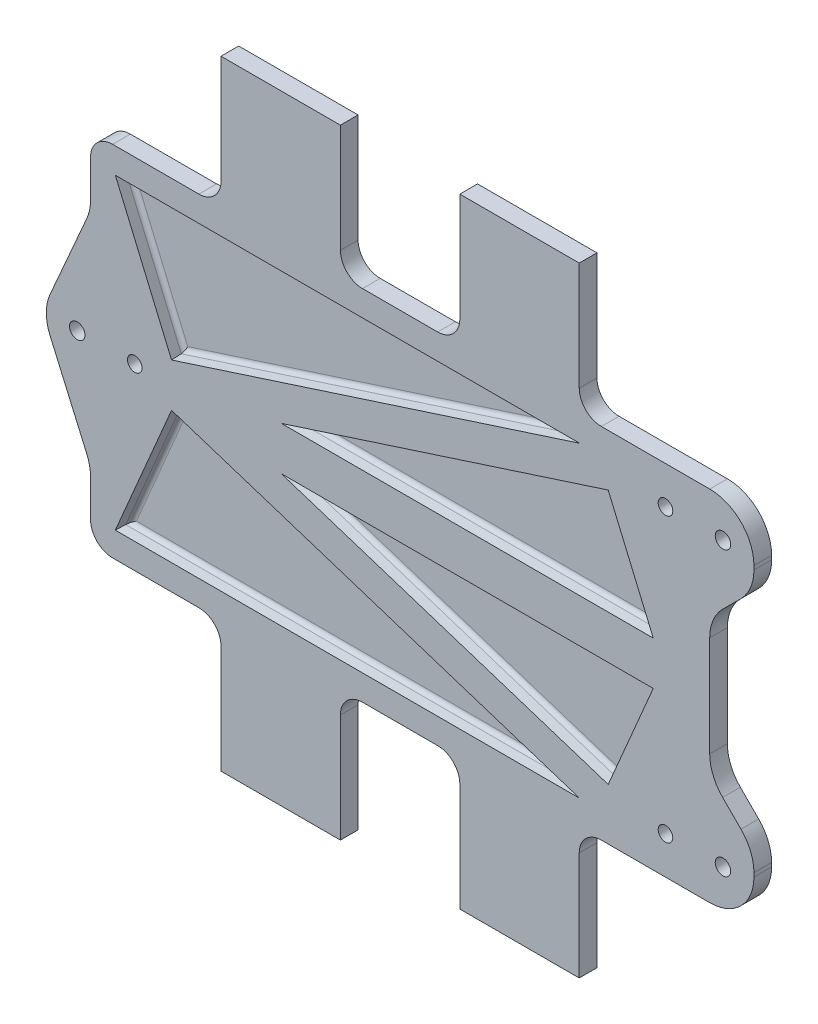
SolidWorks part; units mm, degrees
material "Ceramic Porcelain"
ref_plane "Front Plane" through (0, 0, 0) normal (0, 0, 1) x (1, 0, 0)
ref_plane "Top Plane" through (0, 0, 0) normal (0, 1, 0) x (1, 0, 0)
ref_plane "Right Plane" through (0, 0, 0) normal (1, 0, 0) x (0, 0, -1)
sketch "Sketch1" plane through (0, 0, 0) normal (0, 0, 1) x (1, 0, 0)
  line L0 (140, 70) -> (-19.1725, 70) construction
  line L1 (0, 0) -> (140, 0)
  line L2 (0, 0) -> (0, 42.9273)
  line L3 (0, 140) -> (140, 140)
  line L4 (140, 0) -> (140, 140)
  line L5 (-9.164, 74.0025) -> (-0.836, 93.0702)
  line L6 (-9.164, 65.9975) -> (-0.836, 46.9298)
  line L7 (0, 97.0727) -> (0, 140)
  line L8 (0, 97.0727) -> (0, 42.9273) construction
  arc A0 (-9.164, 65.9975) -> (-9.164, 74.0025) centre (0, 70) cw
  arc A1 (-0.836, 93.0702) -> (0, 97.0727) centre (-10, 97.0727) ccw
  arc A2 (-0.836, 46.9298) -> (0, 42.9273) centre (-10, 42.9273) cw
  point P14 (0, 94.9841)
  dimension "D2" = 10
  dimension "D3" = 10
  dimension "D4" = 10
  dimension "D1" = 140
extrude "Boss-Extrude1" add sketch "Sketch1" along normal blind 4
sketch "Sketch2" plane through (0, 0, 4) normal (0, 0, 1) x (1, 0, 0)
  line L0 (0, 42.9273) -> (0, 0) construction
  line L1 (5, 5) -> (27, 5)
  line L2 (5, 5) -> (5, 27)
  line L3 (5, 27) -> (27, 27)
  line L4 (27, 5) -> (27, 27)
  line L5 (0, 0) -> (140, 0) construction
  dimension "D1" = 22
  dimension "D2" = 5
  dimension "D3" = 5
extrude "Cut-Extrude2" [suppressed] cut sketch "Sketch2" against normal blind 3
chamfer "Chamfer1" [suppressed] distance 3 angle 15
fillet "Fillet3" [suppressed] radius 1
fillet "Fillet4" [suppressed] radius 1
pattern_linear "LPattern1" [suppressed] count 5 spacing 27 count 5 spacing 27 of bodies 103
sketch "Sketch3" plane through (0, 0, 4) normal (0, 0, 1) x (1, 0, 0)
  line L0 (0, 0) -> (140, 0) construction
  line L1 (0, 0) -> (29.5, 0)
  line L2 (0, 0) -> (0, 29.5)
  line L3 (0, 29.5) -> (29.5, 29.5)
  line L4 (29.5, 0) -> (29.5, 29.5)
  line L5 (56.5, 0) -> (83.5, 0)
  line L6 (56.5, 0) -> (56.5, 29.5)
  line L7 (56.5, 29.5) -> (83.5, 29.5)
  line L8 (83.5, 0) -> (83.5, 29.5)
  line L9 (70, 0) -> (70, 140) construction
  line L10 (140, 140) -> (110.5, 140)
  line L11 (140, 140) -> (140, 110.5)
  line L15 (110.5, 0) -> (110.5, 29.5)
  line L16 (140, 29.5) -> (110.5, 29.5)
  line L17 (140, 0) -> (140, 29.5)
  line L18 (140, 0) -> (110.5, 0)
  line L19 (140, 110.5) -> (110.5, 110.5)
  line L20 (110.5, 140) -> (110.5, 110.5)
  line L21 (29.5, 140) -> (29.5, 110.5)
  line L22 (0, 110.5) -> (29.5, 110.5)
  line L23 (0, 140) -> (0, 110.5)
  line L24 (0, 140) -> (29.5, 140)
  line L25 (0, 0) -> (140, 140) construction
  line L31 (83.5, 140) -> (83.5, 110.5)
  line L32 (56.5, 110.5) -> (83.5, 110.5)
  line L33 (56.5, 140) -> (56.5, 110.5)
  line L34 (56.5, 140) -> (83.5, 140)
  dimension "D1" = 29.5
  dimension "D2" = 56.5
  dimension "D3" = 27
extrude "Cut-Extrude3" cut sketch "Sketch3" against normal through all
sketch "Sketch9" plane through (0, 0, 0) normal (0, 0, -1) x (-1, 0, 0)
  line L0 (-140, 110.5) -> (-150, 110.5)
  line L1 (-150, 110.5) -> (-150, 95.5)
  line L2 (-150, 95.5) -> (-140, 85.5)
  line L3 (-140, 29.5) -> (-140, 110.5) construction
  line L4 (-140, 70) -> (-101.7414, 70) construction
  line L5 (-140, 110.5) -> (-140, 85.5)
  line L6 (-140, 29.5) -> (-140, 54.5)
  line L7 (-150, 44.5) -> (-140, 54.5)
  line L8 (-150, 29.5) -> (-150, 44.5)
  line L9 (-140, 29.5) -> (-150, 29.5)
  dimension "D1" = 10
  dimension "D2" = 15
  dimension "D3" = 25
extrude "Boss-Extrude2" add sketch "Sketch9" against normal up to surface (4 mm away) up to face at (53.0607, 70, 4)
fillet "Fillet5" radius 10 6 edges at (150, 29.5, 2) (150, 44.5, 2) (140, 54.5, 2) (150, 95.5, 2) (150, 110.5, 2)
sketch "Sketch10" [suppressed] plane through (0, 0, 6) normal (0, 0, 1) x (1, 0, 0)
  line L0 (127.2327, 102) -> (127.2327, 108.7673)
  line L1 (112.2327, 108.7673) -> (135.7673, 108.7673) construction
  line L2 (127.2327, 108.7673) -> (135.7673, 108.7673)
  line L3 (134, 95.2327) -> (135.7673, 95.2327)
  line L4 (135.7673, 108.7673) -> (135.7673, 85.2327) construction
  line L5 (135.7673, 95.2327) -> (135.7673, 108.7673)
  line L6 (127.2327, 38) -> (127.2327, 31.2327)
  line L7 (135.7673, 31.2327) -> (112.2327, 31.2327) construction
  line L8 (127.2327, 31.2327) -> (135.7673, 31.2327)
  line L9 (135.7673, 31.2327) -> (135.7673, 44.7673)
  line L10 (135.7673, 54.7673) -> (135.7673, 31.2327) construction
  line L11 (135.7673, 44.7673) -> (134, 44.7673)
  line L12 (4.2327, 74.1422) -> (6, 74.1422)
  line L13 (4.2327, 58.2327) -> (4.2327, 81.7673) construction
  line L14 (4.2327, 74.1422) -> (4.2327, 65.8578)
  line L15 (4.2327, 65.8578) -> (6, 65.8578)
  arc A1 (134, 44.7673) -> (127.2327, 38) centre (134, 38) ccw
  arc A2 (6, 65.8578) -> (6, 74.1422) centre (6, 70) ccw
  arc A3 (127.2327, 102) -> (134, 95.2327) centre (134, 102) ccw
extrude "Boss-Extrude3" [suppressed] add sketch "Sketch10" against normal up to surface (3 mm away)
hole_wizard "CSK for M3 Flat Head Machine Screw1" positions "Sketch6" profile "Sketch5" countersink size "M3" standard "Ansi Metric" end condition through all
sketch "Sketch6" plane through (0, 0, 0) normal (0, 0, -1) x (-1, 0, 0)
  line L0 (3.5733, 70) -> (-140, 70) construction
  line L4 (-140, 58.6421) -> (-140, 81.3579) construction
  line L5 (-130, 102) -> (-130, 38) construction
  point P0 (-10, 70)
  point P20 (-130, 102)
  point P22 (-130, 38)
  dimension "D1" = 10
  dimension "D2" = 10
  dimension "D3" = 32
  dimension "D4" = 64
sketch "Sketch5" plane through (10, 70, 0) normal (1, 0, 0) x (0, 1, 0)
  line L0 (0, 0) -> (0, 4)
  line L1 (0, 4) -> (1.65, 4)
  line L2 (1.65, 4) -> (1.65, 1.35)
  line L3 (1.65, 1.35) -> (3, 0)
  line L5 (3, 0) -> (0, 0)
  line L6 (-1.65, 1.35) -> (-3, 0) construction
  line L11 (0, -6.35) -> (0, 107.95) construction
  dimension "Thru Hole Dia." = 3.3
  dimension "Thru Hole Depth" = 4
  dimension "Near C'Sink Dia." = 6
  dimension "Near C'Sink Angle" = 90
sketch "Sketch8" plane through (0, 0, 0) normal (0, 0, -1) x (-1, 0, 0)
  line L0 (-140, 70) -> (10, 70) construction
  line L1 (-140, 58.6421) -> (-140, 81.3579) construction
  line L2 (-130, 102) -> (-143, 102) construction
  line L3 (-130, 38) -> (-143, 38) construction
  arc A0 (9.164, 65.9975) -> (9.164, 74.0025) centre (0, 70) ccw construction
  circle A1 centre (3, 70) radius 1.75
  circle A2 centre (-10, 70) radius 1.65 construction
  circle A3 centre (-143, 102) radius 1.75
  circle A4 centre (-143, 38) radius 1.75
  dimension "D1" = 13
  dimension "D2" = 3.5
  dimension "D3" = 13
extrude "Cut-Extrude4" cut sketch "Sketch8" against normal through all
fillet "Fillet6" radius 5 10 edges at (29.5, 29.5, 2) (83.5, 29.5, 2) (56.5, 29.5, 2) (110.5, 29.5, 2) (29.5, 110.5, 2) (83.5, 110.5, 2) (56.5, 110.5, 2) (110.5, 110.5, 2) (0, 110.5, 2) (0, 29.5, 2)
sketch "Sketch11" plane through (0, 0, 4) normal (0, 0, 1) x (1, 0, 0)
  line L0 (140, 70) -> (-10, 70) construction
  line L1 (140, 58.6421) -> (140, 81.3579) construction
  line L2 (110.5872, 104.7584) -> (5.6009, 104.7584)
  line L3 (5.6009, 104.7584) -> (18.3195, 74.9275)
  line L4 (18.3195, 74.9275) -> (110.5872, 104.7584)
  line L5 (117.0488, 98.8234) -> (43.1382, 74.9275)
  line L6 (43.1382, 74.9275) -> (127.237, 74.9275)
  line L7 (127.237, 74.9275) -> (117.0488, 98.8234)
  line L8 (127.237, 65.0725) -> (117.0488, 41.1766)
  line L9 (43.1382, 65.0725) -> (127.237, 65.0725)
  line L10 (117.0488, 41.1766) -> (43.1382, 65.0725)
  line L11 (18.3195, 65.0725) -> (110.5872, 35.2416)
  line L12 (5.6009, 35.2416) -> (18.3195, 65.0725)
  line L13 (110.5872, 35.2416) -> (5.6009, 35.2416)
  arc A0 (-9.164, 74.0025) -> (-9.164, 65.9975) centre (0, 70) ccw construction
extrude "Cut-Extrude5" cut sketch "Sketch11" against normal offset from surface (3 mm away) 1 up to face at (141.25, 38, 0)
chamfer "Chamfer2" distance 3 angle 5 12 edges at (64.4533, 50.157, 1) (58.094, 35.2416, 1) (11.9602, 50.157, 1) (122.1429, 53.1245, 1) (80.0935, 53.1245, 1) (85.1876, 65.0725, 1) (85.1876, 74.9275, 1) (80.0935, 86.8755, 1) (122.1429, 86.8755, 1) (11.9602, 89.843, 1) (58.094, 104.7584, 1) (64.4533, 89.843, 1) first distance on face at (64.4533, 50.157, 2.5) first distance on face at (58.094, 35.2416, 2.5) first distance on face at (11.9602, 50.157, 2.5) first distance on face at (122.1429, 53.1245, 2.5) first distance on face at (80.0935, 53.1245, 2.5) first distance on face at (85.1876, 65.0725, 2.5) first distance on face at (85.1876, 74.9275, 2.5) first distance on face at (80.0935, 86.8755, 2.5) first distance on face at (122.1429, 86.8755, 2.5) first distance on face at (11.9602, 89.843, 2.5) first distance on face at (58.094, 104.7584, 2.5) first distance on face at (64.4533, 89.843, 2.5)
fillet "Fillet7" radius 1 12 edges at (12.2325, 50.1265, 1) (63.6945, 50.1265, 1) (57.4601, 35.504, 1) (85.8215, 64.81, 1) (121.8706, 53.155, 1) (80.8523, 53.155, 1) (121.8706, 86.845, 1) (85.8215, 75.19, 1) (80.8523, 86.845, 1) (63.6945, 89.8735, 1) (12.2325, 89.8735, 1) (57.4601, 104.496, 1)
